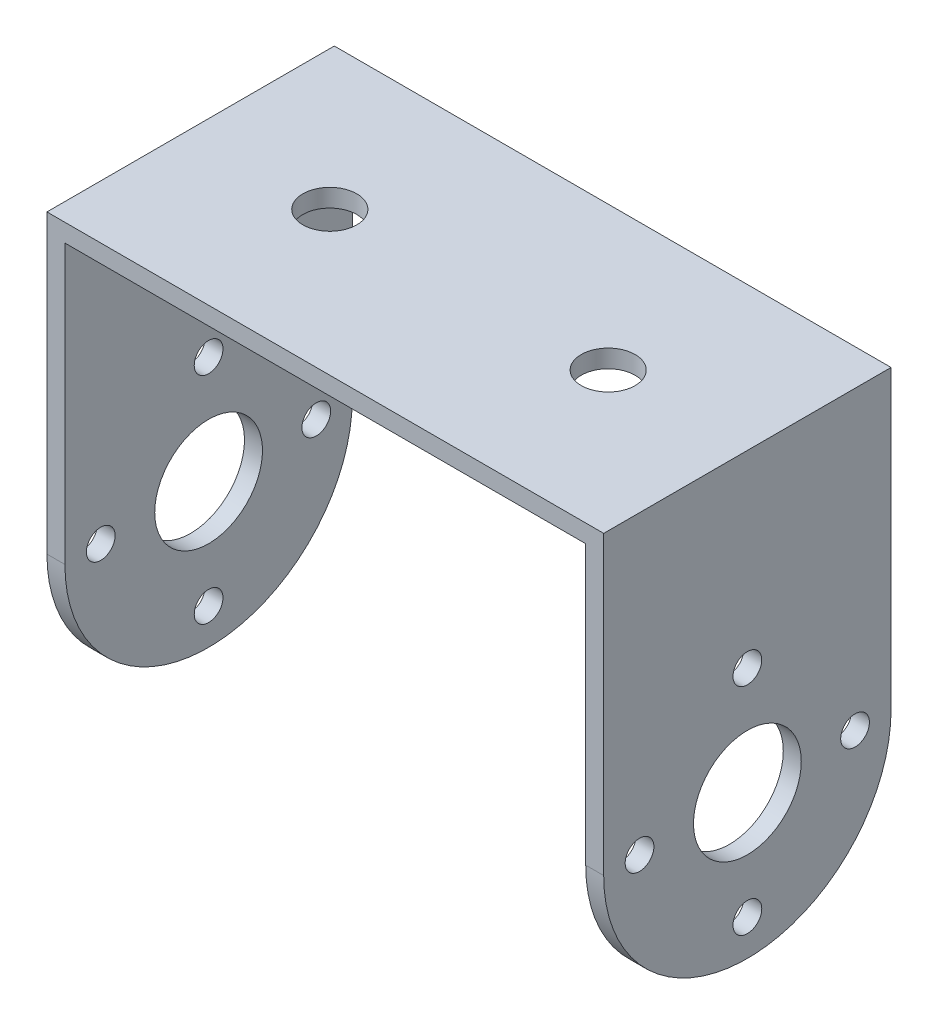
SolidWorks part; units mm, degrees
ref_plane "Front Plane" through (0, 0, 0) normal (0, 0, 1) x (1, 0, 0)
ref_plane "Top Plane" through (0, 0, 0) normal (0, 1, 0) x (1, 0, 0)
ref_plane "Right Plane" through (0, 0, 0) normal (1, 0, 0) x (0, 0, -1)
sketch "Sketch1" plane through (0, 0, 0) normal (1, 0, 0) x (0, 0, -1)
  line L0 (27.5206, 38.7756) -> (27.5206, 55.2756)
  line L1 (35.5206, 38.7756) -> (35.5206, 32.7756) construction
  line L6 (35.5206, 38.7756) -> (41.5159, 38.7756) construction
  line L7 (35.5206, 38.7756) -> (35.5206, 44.7756) construction
  line L8 (35.5206, 38.7756) -> (29.5159, 38.7756) construction
  line L9 (27.5206, 55.2756) -> (43.5206, 55.2756)
  line L10 (43.5206, 55.2756) -> (43.5206, 38.7756)
  arc A0 (27.5206, 38.7756) -> (43.5206, 38.7756) centre (35.5206, 38.7756) ccw
  circle A1 centre (35.5206, 44.7756) radius 0.8
  circle A2 centre (41.5159, 38.7756) radius 0.8
  circle A3 centre (35.5206, 32.7756) radius 0.8
  circle A4 centre (29.5159, 38.7756) radius 0.8
  circle A5 centre (35.5206, 38.7756) radius 3
extrude "Boss-Extrude1" add sketch "Sketch1" along normal blind 31
sketch "Sketch4" plane through (0, 55.2756, 0) normal (0, 1, 0) x (1, 0, 0)
  line L0 (0, 43.5206) -> (31, 43.5206)
  line L1 (31, 43.5206) -> (31, 65.0883)
  line L2 (0, 43.5206) -> (0, 65.0883)
  line L4 (0, 65.0883) -> (0, 81.2361)
  line L5 (31, 81.2361) -> (31, 65.0883)
  arc A0 (31, 81.2361) -> (0, 81.2361) centre (15.5, 81.2361) ccw
extrude "Boss-Extrude2" add sketch "Sketch4" against normal blind 1
sketch "Sketch5" plane through (0, 54.2756, 0) normal (0, -1, 0) x (1, 0, 0)
  circle A0 centre (15.5, -81.2361) radius 8
  circle A1 centre (9.5, -81.2361) radius 0.8
  circle A2 centre (15.5, -75.2361) radius 0.8
  circle A3 centre (21.5, -81.2361) radius 0.8
  circle A4 centre (15.5, -87.2361) radius 0.8
  circle A5 centre (15.5, -81.2361) radius 3
extrude "Cut-Extrude3" cut sketch "Sketch5" against normal blind 1 contours A3 | A4 | A1 | A2
extrude "Cut-Extrude4" cut sketch "Sketch5<3>" against normal blind 1 contours A5
sketch "Sketch5<3>" plane through (0, 54.2756, 0) normal (0, -1, 0) x (1, 0, 0) same geometry as "Sketch5"
sketch "Sketch6" plane through (0, 55.2756, 0) normal (0, 1, 0) x (1, 0, 0)
  line L0 (1.0012, 44.917) -> (29.9988, 44.917)
  line L1 (1.0012, 44.917) -> (1.0012, 26.1243)
  line L3 (29.9988, 44.917) -> (29.9988, 26.1243)
  line L4 (1.0012, 26.1243) -> (29.9988, 26.1243)
  line L5 (1.0012, 44.917) -> (29.9988, 26.1243) construction
  line L6 (29.9988, 44.917) -> (1.0012, 26.1243) construction
extrude "Cut-Extrude6" cut sketch "Sketch6" against normal through all from offset 1 offset against normal yes
sketch "Sketch7" plane through (0, 54.2756, 0) normal (0, -1, 0) x (1, 0, 0)
  line L0 (0, -43.5206) -> (31, -43.5206)
  line L1 (31, -43.5206) -> (31, -99.5377)
  line L2 (31, -99.5377) -> (0, -99.5377)
  line L3 (0, -99.5377) -> (0, -43.5206)
extrude "Cut-Extrude7" cut sketch "Sketch7" against normal through all
sketch "Sketch8" plane through (0, 54.2756, 0) normal (0, -1, 0) x (1, 0, 0)
  circle A0 centre (7.75, -35.5206) radius 1.5
  circle A1 centre (23.25, -35.5206) radius 1.5
extrude "Cut-Extrude8" cut sketch "Sketch8" against normal through all
sketch "Sketch9" plane through (31, 0, 0) normal (1, 0, 0) x (0, 0, -1)
  point P0 (35.5206, 38.7756)
